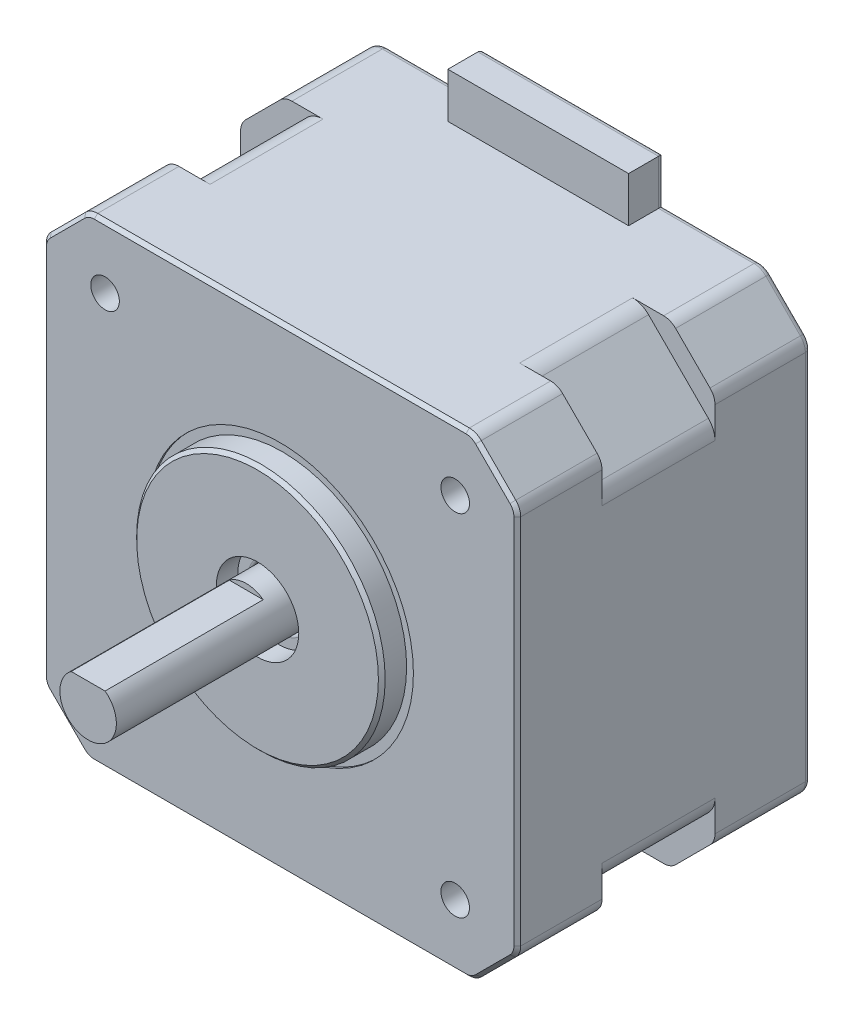
SolidWorks part; units mm, degrees
ref_plane "前视基准面" through (0, 0, 0) normal (0, 0, 1) x (1, 0, 0)
ref_plane "上视基准面" through (0, 0, 0) normal (0, 1, 0) x (1, 0, 0)
ref_plane "右视基准面" through (0, 0, 0) normal (1, 0, 0) x (0, 0, -1)
other "Configuration Table"
sketch "草图1" plane through (0, 0, 0) normal (0, 0, 1) x (1, 0, 0)
  line L1 (-21, 21) -> (21, 21)
  line L2 (-21, 21) -> (-21, -21)
  line L3 (-21, -21) -> (21, -21)
  line L4 (21, 21) -> (21, -21)
  line L5 (-21, 21) -> (21, -21) construction
  line L6 (-21, -21) -> (21, 21) construction
  point P0 (0, 0)
  dimension "D1" = 42
extrude "凸台-拉伸1" add sketch "草图1" along normal blind 26
sketch "草图2" plane through (0, 0, 0) normal (0, 0, -1) x (-1, 0, 0)
  line L0 (-21, 21) -> (21, 21) construction
  line L1 (8, 21) -> (-8, 21)
  line L2 (8, 21) -> (8, 25)
  line L3 (8, 25) -> (-8, 25)
  line L4 (-8, 21) -> (-8, 25)
  line L5 (0, 0) -> (0, 31.1942) construction
  dimension "D1" = 16
  dimension "D2" = 4
extrude "凸台-拉伸2" add sketch "草图2" against normal blind 3.15
sketch "草图3" plane through (0, 0, 0) normal (0, 0, -1) x (-1, 0, 0)
  line L0 (-17.075, 21) -> (-21, 17.075)
  line L1 (-21, 21) -> (-8, 21) construction
  line L2 (-21, -21) -> (-21, 21) construction
  line L3 (17.075, 21) -> (21, 17.075)
  line L4 (8, 21) -> (21, 21) construction
  line L5 (21, 21) -> (21, -21) construction
  line L6 (21, -17.075) -> (17.075, -21)
  line L7 (21, -21) -> (-21, -21) construction
  line L8 (-21, -17.075) -> (-17.075, -21)
  line L9 (-17.075, 21) -> (-21, 21)
  line L10 (-21, 21) -> (-21, 17.075)
  line L11 (17.075, 21) -> (21, 21)
  line L12 (21, 21) -> (21, 17.075)
  line L13 (21, -17.075) -> (21, -21)
  line L14 (21, -21) -> (17.075, -21)
  line L15 (-21, -17.075) -> (-21, -21)
  line L16 (-21, -21) -> (-17.075, -21)
  dimension "D1" = 3.925
extrude "切除-拉伸1" cut sketch "草图3" against normal up to next
sketch "草图4" plane through (0, 0, 0) normal (0, 0, -1) x (-1, 0, 0)
  line L0 (-21, 14.532) -> (-14.532, 21)
  line L1 (-21, -17.075) -> (-21, 17.075) construction
  line L2 (-17.075, 21) -> (-8, 21) construction
  line L3 (-14.532, 21) -> (-21, 21)
  line L4 (-21, 21) -> (-21, 14.532)
  line L5 (14.532, 21) -> (21, 14.532)
  line L6 (8, 21) -> (17.075, 21) construction
  line L7 (21, 17.075) -> (21, -17.075) construction
  line L8 (21, 14.532) -> (21, 21)
  line L9 (21, 21) -> (14.532, 21)
  line L10 (21, -14.532) -> (14.532, -21)
  line L11 (17.075, -21) -> (-17.075, -21) construction
  line L12 (14.532, -21) -> (21, -21)
  line L13 (21, -21) -> (21, -14.532)
  line L14 (-14.532, -21) -> (-21, -14.532)
  line L15 (-21, -14.532) -> (-21, -21)
  line L16 (-21, -21) -> (-14.532, -21)
  dimension "D1" = 6.468
extrude "切除-拉伸2" cut sketch "草图4" against normal blind 10 from offset 8.5 offset against normal yes
fillet "圆角2" radius 1.5 16 edges at (-21, -17.075, 22.25) (-17.075, -21, 22.25) (-17.075, -21, 4.25) (-21, -17.075, 4.25) (-21, 17.075, 22.25) (-17.075, 21, 22.25) (-17.075, 21, 4.25) (-21, 17.075, 4.25) (17.075, -21, 4.25) (21, -17.075, 4.25) (17.075, -21, 22.25) (21, -17.075, 22.25) (21, 17.075, 4.25) (17.075, 21, 4.25) (21, 17.075, 22.25) (17.075, 21, 22.25)
fillet "圆角3" radius 2 8 edges at (21, -14.532, 13.5) (14.532, -21, 13.5) (-14.532, -21, 13.5) (-21, -14.532, 13.5) (14.532, 21, 13.5) (21, 14.532, 13.5) (-21, 14.532, 13.5) (-14.532, 21, 13.5)
sketch "草图10" plane through (0, 0, 26) normal (0, 0, 1) x (1, 0, 0)
  circle A0 centre (0, 0) radius 11.8
  dimension "D1" = 23.6
extrude "切除-拉伸5" cut sketch "草图10" against normal blind 0.2
sketch "草图11" plane through (0, 0, 25.8) normal (0, 0, 1) x (1, 0, 0)
  circle A0 centre (0, 0) radius 11
  circle A1 centre (0, 0) radius 3.65
  dimension "D1" = 22
  dimension "D2" = 7.3
extrude "凸台-拉伸7" add sketch "草图11" along normal blind 2.2
sketch "草图12" plane through (0, 0, 25.8) normal (0, 0, 1) x (1, 0, 0)
  circle A0 centre (0, 0) radius 2.5
  circle A1 centre (0, 0) radius 3.65
  circle A2 centre (0, 0) radius 3.65
  dimension "D2" = 5
  dimension "D1" = 0
extrude "凸台-拉伸8" add sketch "草图12" along normal blind 0.3
fillet "圆角4" radius 0.3 1 edges at (2.5, 0, 26.1)
sketch "草图13" plane through (0, 0, 25.8) normal (0, 0, 1) x (1, 0, 0)
  circle A0 centre (0, 0) radius 2.5
  dimension "D1" = 5
extrude "凸台-拉伸9" add sketch "草图13" along normal blind 17.2
sketch "草图14" plane through (0, 0, 43) normal (0, 0, 1) x (1, 0, 0)
  line L0 (-1.5, 2) -> (1.5, 2)
  circle A0 centre (0, 0) radius 2.5 construction
  dimension "D1" = 3
extrude "切除-拉伸6" cut sketch "草图14" against normal blind 14 and the other way through all
sketch "草图15" plane through (0, 0, 26) normal (0, 0, 1) x (1, 0, 0)
  line L1 (15.5, -15.5) -> (-15.5, -15.5) construction
  line L2 (15.5, -15.5) -> (15.5, 15.5) construction
  line L3 (15.5, 15.5) -> (-15.5, 15.5) construction
  line L4 (-15.5, -15.5) -> (-15.5, 15.5) construction
  line L5 (15.5, -15.5) -> (-15.5, 15.5) construction
  line L6 (15.5, 15.5) -> (-15.5, -15.5) construction
  circle A0 centre (-15.5, 15.5) radius 1.2645
  circle A1 centre (15.5, 15.5) radius 1.2645
  circle A2 centre (15.5, -15.5) radius 1.2645
  circle A3 centre (-15.5, -15.5) radius 1.2645
  point P0 (0, 0)
  dimension "D2" = 2.529
  dimension "D1" = 31
extrude "切除-拉伸7" cut sketch "草图15" against normal blind 4.4
chamfer "倒角4" distance 0.3 angle 45 1 edges at (11, 0, 28)
chamfer "倒角5" distance 0.3 angle 45 16 edges at (-21, 0, 26) (-20.8858, -17.0277, 26) (-20.8858, 17.0277, 26) (-19.0375, -19.0375, 26) (-19.0375, 19.0375, 26) (-17.0277, -20.8858, 26) (-17.0277, 20.8858, 26) (0, -21, 26) (0, 21, 26) (17.0277, -20.8858, 26) (17.0277, 20.8858, 26) (19.0375, -19.0375, 26) (19.0375, 19.0375, 26) (20.8858, -17.0277, 26) (20.8858, 17.0277, 26) (21, 0, 26)
fillet "圆角5" radius 0.5 20 edges at (-12.2268, 21, 0) (-17.0277, 20.8858, 0) (-19.0375, 19.0375, 0) (-20.8858, 17.0277, 0) (-21, 0, 0) (-20.8858, -17.0277, 0) (-19.0375, -19.0375, 0) (-17.0277, -20.8858, 0) (0, -21, 0) (17.0277, -20.8858, 0) (19.0375, -19.0375, 0) (20.8858, -17.0277, 0) (12.2268, 21, 0) (17.0277, 20.8858, 0) (19.0375, 19.0375, 0) (20.8858, 17.0277, 0) (-8, 23, 0) (0, 25, 0) (8, 23, 0) (21, 0, 0)
